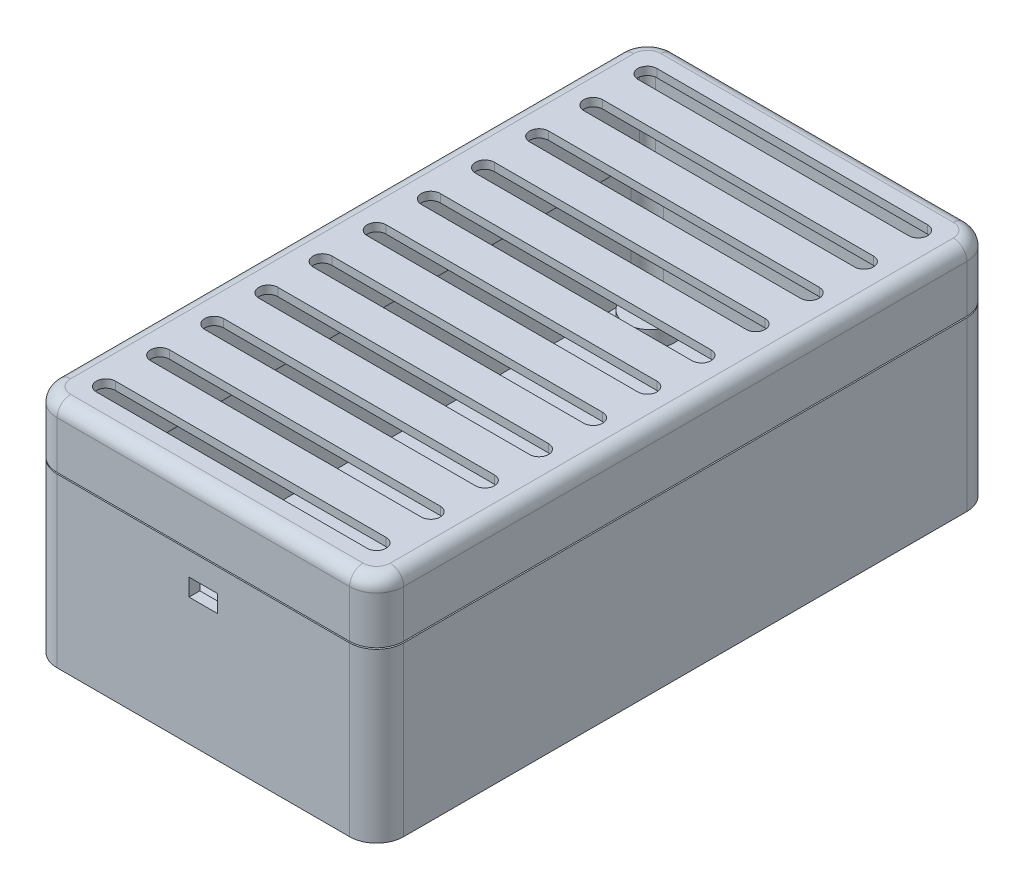
SolidWorks part; units mm, degrees
ref_plane "Front Plane" through (0, 0, 0) normal (0, 0, 1) x (1, 0, 0)
ref_plane "Top Plane" through (0, 0, 0) normal (0, 1, 0) x (1, 0, 0)
ref_plane "Right Plane" through (0, 0, 0) normal (1, 0, 0) x (0, 0, -1)
sketch "Sketch1" plane through (0, 0, 0) normal (0, 1, 0) x (1, 0, 0)
  line L0 (0, 0) -> (0, 19.2016) construction
  line L1 (-25.3206, 52.85) -> (25.3206, 52.85) construction
  line L2 (-25.3206, 52.85) -> (-25.3206, -52.85) construction
  line L3 (-25.3206, -52.85) -> (25.3206, -52.85) construction
  line L4 (25.3206, 52.85) -> (25.3206, -52.85) construction
  line L5 (-25.3206, 52.85) -> (25.3206, -52.85) construction
  line L6 (-25.3206, -52.85) -> (25.3206, 52.85) construction
  line L7 (21.5, 49.05) -> (-21.5, 49.05) construction
  line L8 (-23.5, 51.05) -> (23.5, 51.05) construction
  line L9 (0, 0) -> (38.1053, 0) construction
  line L10 (-23.5, 47.05) -> (-23.5, -47.05) construction
  line L12 (27, 55) -> (-27, 55)
  line L13 (30, 52) -> (30, -52)
  line L14 (27, -55) -> (-27, -55)
  line L15 (-30, 52) -> (-30, -52)
  line L16 (30, 55) -> (-30, -55) construction
  line L17 (30, -55) -> (-30, 55) construction
  circle A0 centre (-23.5, 49.05) radius 2
  circle A1 centre (23.5, 49.05) radius 2
  circle A2 centre (23.5, -49.05) radius 2
  circle A3 centre (-23.5, -49.05) radius 2
  circle A4 centre (-23.5, 49.05) radius 4.5
  circle A5 centre (23.5, 49.05) radius 4.5
  circle A6 centre (-23.5, -49.05) radius 4.5
  circle A7 centre (23.5, -49.05) radius 4.5
  arc A8 (27, 55) -> (30, 52) centre (27, 52) cw
  arc A9 (30, -52) -> (27, -55) centre (27, -52) cw
  arc A10 (-30, -52) -> (-27, -55) centre (-27, -52) ccw
  arc A11 (-30, 52) -> (-27, 55) centre (-27, 52) cw
  point P0 (0, 0)
  dimension "D1" = 43
  dimension "D3" = 4
  dimension "D8" = 3
  dimension "D2" = 1.8
  dimension "D4" = 94.1
  dimension "D6" = 110
  dimension "D7" = 60
  dimension "D5" = 2.5
extrude "Boss-Extrude1" add sketch "Sketch1" against normal blind 3 contours A0 | L14 A10 L15 A11 L12 A8 L13 A9 | A3 | A1 | A2 region at (-23.5, 0, -49.05)
extrude "Boss-Extrude2" add sketch "Sketch1<3>" along normal blind 3 contours A4 A0 | A5 A1 | A7 A2 | A6 | A3 region at (-27.8727, 0, -49.05) region at (19.1273, 0, -49.05) region at (19.1273, 0, 49.05)
sketch "Sketch1<3>" plane through (0, 0, 0) normal (0, 1, 0) x (1, 0, 0) same geometry as "Sketch1"
sketch "Sketch2" plane through (0, 0, 0) normal (0, 1, 0) x (1, 0, 0)
  line L12 (32, -52) -> (32, 52)
  line L13 (27, 57) -> (-27, 57)
  line L15 (-27, -57) -> (27, -57)
  line L20 (-32, 52) -> (-32, -52)
  line L21 (-27, -57) -> (27, -57)
  line L22 (32, -52) -> (32, 52)
  line L23 (27, 57) -> (-27, 57)
  line L24 (30, -52) -> (30, 52)
  line L25 (27, 55) -> (-27, 55)
  line L26 (-30, 52) -> (-30, -52)
  line L27 (-27, -55) -> (27, -55)
  line L28 (30, -52) -> (30, 52)
  line L29 (27, 55) -> (-27, 55)
  line L30 (-30, 52) -> (-30, -52)
  line L31 (-27, -55) -> (27, -55)
  arc A12 (27, -57) -> (32, -52) centre (27, -52) ccw
  arc A13 (32, 52) -> (27, 57) centre (27, 52) ccw
  arc A14 (-27, 57) -> (-32, 52) centre (-27, 52) ccw
  arc A15 (-32, -52) -> (-27, -57) centre (-27, -52) ccw
  arc A20 (-32, -52) -> (-27, -57) centre (-27, -52) ccw
  arc A21 (27, -57) -> (32, -52) centre (27, -52) ccw
  arc A22 (32, 52) -> (27, 57) centre (27, 52) ccw
  arc A23 (-27, 57) -> (-32, 52) centre (-27, 52) ccw
  arc A24 (27, -55) -> (30, -52) centre (27, -52) ccw
  arc A25 (30, 52) -> (27, 55) centre (27, 52) ccw
  arc A26 (-27, 55) -> (-30, 52) centre (-27, 52) ccw
  arc A27 (-30, -52) -> (-27, -55) centre (-27, -52) ccw
  arc A28 (27, -55) -> (30, -52) centre (27, -52) ccw
  arc A29 (30, 52) -> (27, 55) centre (27, 52) ccw
  arc A30 (-27, 55) -> (-30, 52) centre (-27, 52) ccw
  arc A31 (-30, -52) -> (-27, -55) centre (-27, -52) ccw
  dimension "D2" = 0
  dimension "D3" = 2
extrude "Boss-Extrude3" add sketch "Sketch2" along normal blind 28 and the other way up to surface (3 mm away) contours L20 A15 L15 A12 L12 A13 L13 A14 A31 L30 A30 L29 A29 L28 A28 L31 region at (29.6111, 0, 54.6111) other way up to face at (23.5, -3, 51.05)
chamfer "Chamfer1" distance 3.5 angle 30 4 edges at (-23.5, -3, 47.05) (23.5, -3, 51.05) (-23.5, -3, -47.05) (23.5, -3, -51.05) first distance on face at (23.5, -3, 51.05)
sketch "Sketch3" plane through (0, 0, -57) normal (0, 0, -1) x (-1, 0, 0)
  line L1 (-3.5, 12) -> (7.25, 12)
  line L2 (-3.5, 12) -> (-3.5, 6)
  line L3 (-3.5, 6) -> (7.25, 6)
  line L4 (7.25, 12) -> (7.25, 6)
  line L5 (-19, 3) -> (-28, 3) construction
  line L6 (0, 0) -> (0, 28) construction
  line L7 (-27, 28) -> (27, 28) construction
  line L8 (-28.5, 0) -> (28.5, 0) construction
  point P14 (0, 0)
  dimension "D1" = 3
  dimension "D2" = 57
  dimension "D3" = 25
  dimension "D4" = 21.25
  dimension "D5" = 6
extrude "Cut-Extrude4" cut sketch "Sketch3" along normal mid plane 5
sketch "Sketch4" plane through (0, 0, 57) normal (0, 0, 1) x (1, 0, 0)
  line L0 (0, 0) -> (0, 33.5553) construction
  line L1 (-2.65, 23.7) -> (2.65, 23.7)
  line L2 (-2.65, 23.7) -> (-2.65, 20.5)
  line L3 (-2.65, 20.5) -> (2.65, 20.5)
  line L4 (2.65, 23.7) -> (2.65, 20.5)
  line L5 (27, 0) -> (-27, 0) construction
  line L6 (-19, 3) -> (-28, 3) construction
  dimension "D1" = 5.3
  dimension "D2" = 3.2
  dimension "D3" = 17.5
extrude "Cut-Extrude5" cut sketch "Sketch4" against normal mid plane 5
sketch "Sketch5" plane through (0, 28, 0) normal (0, 1, 0) x (1, 0, 0)
  line L4 (-28.5, 52) -> (-28.5, -52)
  line L5 (-27, -53.5) -> (27, -53.5)
  line L6 (28.5, -52) -> (28.5, 52)
  line L7 (27, 53.5) -> (-27, 53.5)
  line L8 (-27, -54.5) -> (27, -54.5)
  line L9 (29.5, -52) -> (29.5, 52)
  line L10 (27, 54.5) -> (-27, 54.5)
  line L11 (-29.5, 52) -> (-29.5, -52)
  line L12 (-27, -54.5) -> (27, -54.5)
  line L13 (29.5, -52) -> (29.5, 52)
  line L14 (27, 54.5) -> (-27, 54.5)
  line L15 (-29.5, 52) -> (-29.5, -52)
  arc A4 (-28.5, -52) -> (-27, -53.5) centre (-27, -52) ccw
  arc A5 (27, -53.5) -> (28.5, -52) centre (27, -52) ccw
  arc A6 (28.5, 52) -> (27, 53.5) centre (27, 52) ccw
  arc A7 (-27, 53.5) -> (-28.5, 52) centre (-27, 52) ccw
  arc A8 (-29.5, -52) -> (-27, -54.5) centre (-27, -52) ccw
  arc A9 (27, -54.5) -> (29.5, -52) centre (27, -52) ccw
  arc A10 (29.5, 52) -> (27, 54.5) centre (27, 52) ccw
  arc A11 (-27, 54.5) -> (-29.5, 52) centre (-27, 52) ccw
  arc A12 (-29.5, -52) -> (-27, -54.5) centre (-27, -52) ccw
  arc A13 (27, -54.5) -> (29.5, -52) centre (27, -52) ccw
  arc A14 (29.5, 52) -> (27, 54.5) centre (27, 52) ccw
  arc A15 (-27, 54.5) -> (-29.5, 52) centre (-27, 52) ccw
  dimension "D1" = 0.5
  dimension "D2" = 1
extrude "Boss-Extrude4" add sketch "Sketch5" against normal blind 5 and the other way blind 10 separate body
sketch "Sketch6" plane through (0, 38, 0) normal (0, 1, 0) x (1, 0, 0)
  line L0 (-32, 52) -> (-32, -52)
  line L1 (-27, -57) -> (27, -57)
  line L2 (32, -52) -> (32, 52)
  line L3 (27, 57) -> (-27, 57)
  line L4 (-27, -54.5) -> (27, -54.5)
  line L5 (29.5, -52) -> (29.5, 52)
  line L6 (27, 54.5) -> (-27, 54.5)
  line L7 (-29.5, 52) -> (-29.5, -52)
  line L8 (-27, -54.5) -> (27, -54.5)
  line L9 (29.5, -52) -> (29.5, 52)
  line L10 (27, 54.5) -> (-27, 54.5)
  line L11 (-29.5, 52) -> (-29.5, -52)
  arc A0 (-27, 57) -> (-32, 52) centre (-27, 52) ccw
  arc A1 (-32, -52) -> (-27, -57) centre (-27, -52) ccw
  arc A2 (27, -57) -> (32, -52) centre (27, -52) ccw
  arc A3 (32, 52) -> (27, 57) centre (27, 52) ccw
  arc A4 (-29.5, -52) -> (-27, -54.5) centre (-27, -52) ccw
  arc A5 (27, -54.5) -> (29.5, -52) centre (27, -52) ccw
  arc A6 (29.5, 52) -> (27, 54.5) centre (27, 52) ccw
  arc A7 (-27, 54.5) -> (-29.5, 52) centre (-27, 52) ccw
  arc A8 (-29.5, -52) -> (-27, -54.5) centre (-27, -52) ccw
  arc A9 (27, -54.5) -> (29.5, -52) centre (27, -52) ccw
  arc A10 (29.5, 52) -> (27, 54.5) centre (27, 52) ccw
  arc A11 (-27, 54.5) -> (-29.5, 52) centre (-27, 52) ccw
  dimension "D1" = 0
  dimension "D2" = 2.5
extrude "Boss-Extrude5" add sketch "Sketch6" against normal blind 9.75
sketch "Sketch7" plane through (0, 38, 0) normal (0, 1, 0) x (1, 0, 0)
  line L4 (-32, 52) -> (-32, -52)
  line L5 (-27, -57) -> (27, -57)
  line L6 (32, -52) -> (32, 52)
  line L7 (27, 57) -> (-27, 57)
  line L8 (-32, 52) -> (-32, -52)
  line L9 (-27, -57) -> (27, -57)
  line L10 (32, -52) -> (32, 52)
  line L11 (27, 57) -> (-27, 57)
  arc A4 (-27, 57) -> (-32, 52) centre (-27, 52) ccw
  arc A5 (-32, -52) -> (-27, -57) centre (-27, -52) ccw
  arc A6 (27, -57) -> (32, -52) centre (27, -52) ccw
  arc A7 (32, 52) -> (27, 57) centre (27, 52) ccw
  arc A8 (-27, 57) -> (-32, 52) centre (-27, 52) ccw
  arc A9 (-32, -52) -> (-27, -57) centre (-27, -52) ccw
  arc A10 (27, -57) -> (32, -52) centre (27, -52) ccw
  arc A11 (32, 52) -> (27, 57) centre (27, 52) ccw
  dimension "D1" = 0
extrude "Boss-Extrude6" add sketch "Sketch7" along normal blind 1.5
fillet "Fillet1" radius 2.5 8 edges at (0, 39.5, -57) (30.5355, 39.5, -55.5355) (32, 39.5, 0) (30.5355, 39.5, 55.5355) (0, 39.5, 57) (-30.5355, 39.5, 55.5355) (-32, 39.5, 0) (-30.5355, 39.5, -55.5355)
sketch "Sketch8" plane through (0, 39.5, 0) normal (0, 1, 0) x (1, 0, 0)
  line L0 (-25, 50) -> (25, 50) construction
  line L1 (-25, 51.75) -> (25, 51.75)
  line L2 (-25, 48.25) -> (25, 48.25)
  line L3 (0, 0) -> (52.602, 0) construction
  line L4 (-25, 40) -> (25, 40) construction
  line L5 (-25, 41.75) -> (25, 41.75)
  line L6 (-25, 38.25) -> (25, 38.25)
  line L7 (-25, 30) -> (25, 30) construction
  line L8 (-25, 31.75) -> (25, 31.75)
  line L9 (-25, 28.25) -> (25, 28.25)
  line L10 (-25, 20) -> (25, 20) construction
  line L11 (-25, 21.75) -> (25, 21.75)
  line L12 (-25, 18.25) -> (25, 18.25)
  line L13 (-25, 10) -> (25, 10) construction
  line L14 (-25, 11.75) -> (25, 11.75)
  line L15 (-25, 8.25) -> (25, 8.25)
  line L16 (-25, 0) -> (25, 0) construction
  line L17 (-25, 1.75) -> (25, 1.75)
  line L18 (-25, -1.75) -> (25, -1.75)
  line L19 (-25, -10) -> (25, -10) construction
  line L20 (-25, -8.25) -> (25, -8.25)
  line L21 (-25, -11.75) -> (25, -11.75)
  line L22 (-25, -20) -> (25, -20) construction
  line L23 (-25, -18.25) -> (25, -18.25)
  line L24 (-25, -21.75) -> (25, -21.75)
  line L25 (-25, -30) -> (25, -30) construction
  line L26 (-25, -28.25) -> (25, -28.25)
  line L27 (-25, -31.75) -> (25, -31.75)
  line L28 (-25, -40) -> (25, -40) construction
  line L29 (-25, -38.25) -> (25, -38.25)
  line L30 (-25, -41.75) -> (25, -41.75)
  line L31 (-25, -50) -> (25, -50) construction
  line L32 (-25, -48.25) -> (25, -48.25)
  line L33 (-25, -51.75) -> (25, -51.75)
  arc A0 (-25, 51.75) -> (-25, 48.25) centre (-25, 50) ccw
  arc A1 (25, 48.25) -> (25, 51.75) centre (25, 50) ccw
  arc A2 (-25, 41.75) -> (-25, 38.25) centre (-25, 40) ccw
  arc A3 (25, 38.25) -> (25, 41.75) centre (25, 40) ccw
  arc A4 (-25, 31.75) -> (-25, 28.25) centre (-25, 30) ccw
  arc A5 (25, 28.25) -> (25, 31.75) centre (25, 30) ccw
  arc A6 (-25, 21.75) -> (-25, 18.25) centre (-25, 20) ccw
  arc A7 (25, 18.25) -> (25, 21.75) centre (25, 20) ccw
  arc A8 (-25, 11.75) -> (-25, 8.25) centre (-25, 10) ccw
  arc A9 (25, 8.25) -> (25, 11.75) centre (25, 10) ccw
  arc A10 (-25, 1.75) -> (-25, -1.75) centre (-25, 0) ccw
  arc A11 (25, -1.75) -> (25, 1.75) centre (25, 0) ccw
  arc A12 (-25, -8.25) -> (-25, -11.75) centre (-25, -10) ccw
  arc A13 (25, -11.75) -> (25, -8.25) centre (25, -10) ccw
  arc A14 (-25, -18.25) -> (-25, -21.75) centre (-25, -20) ccw
  arc A15 (25, -21.75) -> (25, -18.25) centre (25, -20) ccw
  arc A16 (-25, -28.25) -> (-25, -31.75) centre (-25, -30) ccw
  arc A17 (25, -31.75) -> (25, -28.25) centre (25, -30) ccw
  arc A18 (-25, -38.25) -> (-25, -41.75) centre (-25, -40) ccw
  arc A19 (25, -41.75) -> (25, -38.25) centre (25, -40) ccw
  arc A20 (-25, -48.25) -> (-25, -51.75) centre (-25, -50) ccw
  arc A21 (25, -51.75) -> (25, -48.25) centre (25, -50) ccw
  point P2 (0, 50)
  point P13 (0, 40)
  point P20 (0, 30)
  point P27 (0, 20)
  point P34 (0, 10)
  point P41 (0, 0)
  point P48 (0, -10)
  point P55 (0, -20)
  point P62 (0, -30)
  point P69 (0, -40)
  point P76 (0, -50)
  dimension "D1" = 50
  dimension "D2" = 3.5
  dimension "D3" = 50
  dimension "D4" = 11
extrude "Cut-Extrude6" cut sketch "Sketch8" against normal through all both and the other way through all
